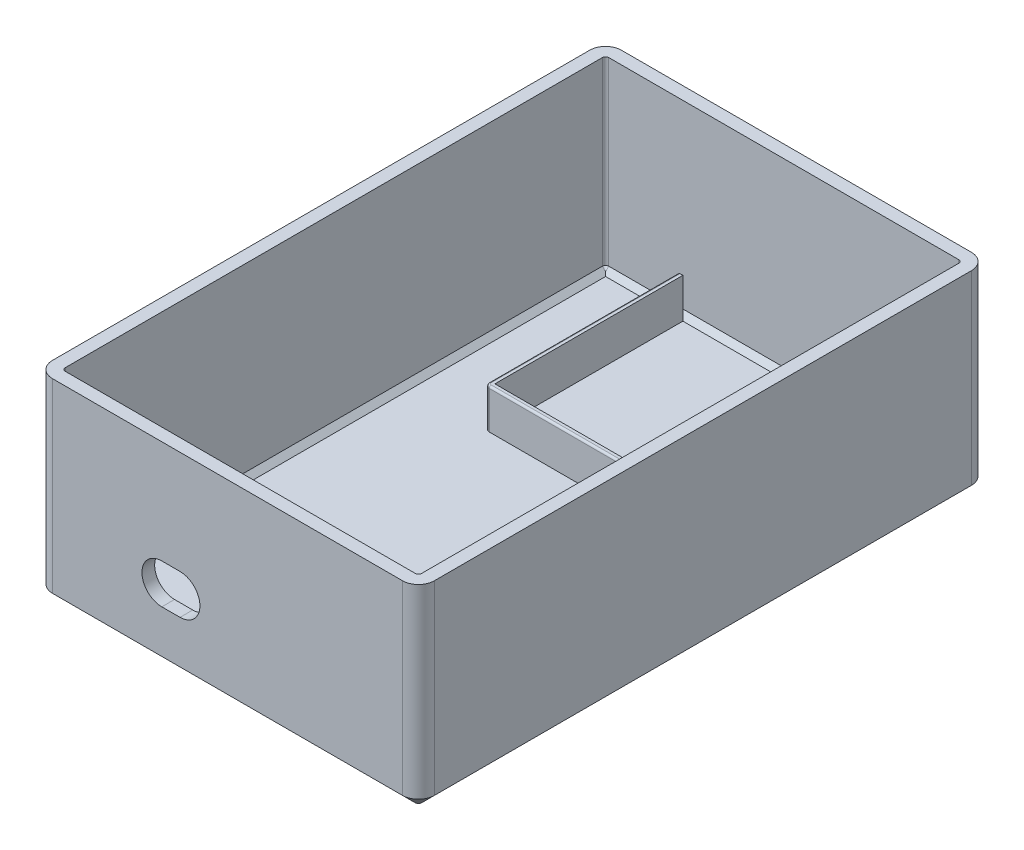
SolidWorks part; units mm, degrees
ref_plane "Front Plane" through (0, 0, 0) normal (0, 0, 1) x (1, 0, 0)
ref_plane "Top Plane" through (0, 0, 0) normal (0, 1, 0) x (1, 0, 0)
ref_plane "Right Plane" through (0, 0, 0) normal (1, 0, 0) x (0, 0, -1)
sketch "Sketch1" plane through (0, 0, 0) normal (0, 1, 0) x (1, 0, 0)
  line L1 (-25.5282, 55.8435) -> (70.5636, 55.8435)
  line L2 (-25.5282, 55.8435) -> (-25.5282, -87.3412)
  line L3 (-25.5282, -87.3412) -> (70.5636, -87.3412)
  line L4 (70.5636, 55.8435) -> (70.5636, -87.3412)
extrude "Boss-Extrude1" add sketch "Sketch1" along normal blind 50
fillet "Fillet1" radius 4 4 edges at (70.5636, 25, -55.8435) (70.5636, 25, 87.3412) (-25.5282, 25, 87.3412) (-25.5282, 25, -55.8435)
chamfer "Chamfer1" distance 3.2 angle 45 8 edges at (22.5177, 0, -55.8435) (-25.5282, 0, 15.7489) (22.5177, 0, 87.3412) (-24.3566, 0, 86.1697) (-24.3566, 0, -54.6719) (69.392, 0, 86.1697) (69.392, 0, -54.6719) (70.5636, 0, 15.7489)
shell "Shell2" thickness 3.2 removed face at (22.5177, 50, 15.7489)
sketch "Sketch2" plane through (0, 0, 87.3412) normal (0, 0, 1) x (1, 0, 0)
  line L0 (5.9734, 19.0214) -> (10.5603, 19.0214) construction
  line L1 (5.9734, 24.0214) -> (10.5603, 24.0214)
  line L2 (5.9734, 14.0214) -> (10.5603, 14.0214)
  arc A0 (5.9734, 24.0214) -> (5.9734, 14.0214) centre (5.9734, 19.0214) ccw
  arc A1 (10.5603, 14.0214) -> (10.5603, 24.0214) centre (10.5603, 19.0214) ccw
  spline S0 degree 5 poles (8.2168, 16.6) (7.51, 16.6) (6.8025, 16.8768) (6.2436, 17.4363) (5.6901, 18.85) (6.2436, 20.2637) (6.8025, 20.8232) (7.51, 21.1) (8.2168, 21.1) knots 0 0 0 0 0 0 0.003511 0.003511 0.003511 0.007022 0.007022 0.007022 0.007022 0.007022 0.007022 weights 1 1 1 1 1 1 1 1 1 construction
  spline S1 degree 5 poles (8.3168, 16.6) (9.0237, 16.6) (9.7312, 16.8768) (10.2901, 17.4363) (10.8436, 18.85) (10.2901, 20.2637) (9.7312, 20.8232) (9.0237, 21.1) (8.3168, 21.1) knots 0 0 0 0 0 0 0.003511 0.003511 0.003511 0.007022 0.007022 0.007022 0.007022 0.007022 0.007022 weights 1 1 1 1 1 1 1 1 1 construction
  point P6 (8.2668, 19.0214)
extrude "Cut-Extrude1" cut sketch "Sketch2" against normal up to next
sketch "Sketch4" plane through (0, 3.2, 0) normal (0, 1, 0) x (1, 0, 0)
  line L0 (-21.0027, 51.318) -> (66.0381, 51.318) construction
  line L1 (-1.5364, 51.318) -> (-2.7364, 51.318)
  line L2 (-1.5364, 51.318) -> (-1.5364, 3.2346)
  line L3 (-1.5364, 3.2346) -> (-2.7364, 3.2346)
  line L4 (-2.7364, 51.318) -> (-2.7364, 3.2346)
  line L5 (-1.1364, 7.9935) -> (-1.1364, 48.6435) construction
  dimension "D1" = 0
  dimension "D2" = 0.4
  dimension "D3" = 1.2
extrude "Boss-Extrude6" add sketch "Sketch4" along normal blind 10
sketch "Sketch5" plane through (0, 3.2, 0) normal (0, 1, 0) x (1, 0, 0)
  line L0 (65.8636, 4.4935) -> (-0.1364, 4.4935) construction
  line L1 (66.0381, 2.7935) -> (-2.7364, 2.7935)
  line L2 (66.0381, 2.7935) -> (66.0381, 3.9935)
  line L3 (66.0381, 3.9935) -> (-2.7364, 3.9935)
  line L4 (-2.7364, 2.7935) -> (-2.7364, 3.9935)
  line L5 (-2.7364, 51.318) -> (-2.7364, 3.2346) construction
  line L6 (-1.3982, 2.7935) -> (-2.7537, 2.7935) construction
  line L8 (66.0381, 51.318) -> (66.0381, -82.8158) construction
  arc A0 (-2.7537, 2.7935) -> (-2.7364, 3.6439) centre (18.166, 2.7935) cw construction
  dimension "D1" = 0.5
  dimension "D2" = 1.2
  dimension "D3" = 0
  dimension "D4" = 0
extrude "Boss-Extrude7" add sketch "Sketch5" along normal blind 10
fillet "Fillet14" radius 1 1 edges at (-2.7364, 8.2, -2.7935) type face fillet first side face at (31.6508, 8.2, -2.7935) second side face at (-2.7364, 8.2, -27.0557)
fillet "Fillet15" radius 0.5 2 edges at (-2.7364, 13.2, -27.5557) (32.1508, 13.2, -2.7935) type face fillet first side face at (-2.7364, 8.2, -27.5557) first side face at (32.1508, 8.2, -2.7935) second side face at (17.3696, 13.2, -17.1137)
